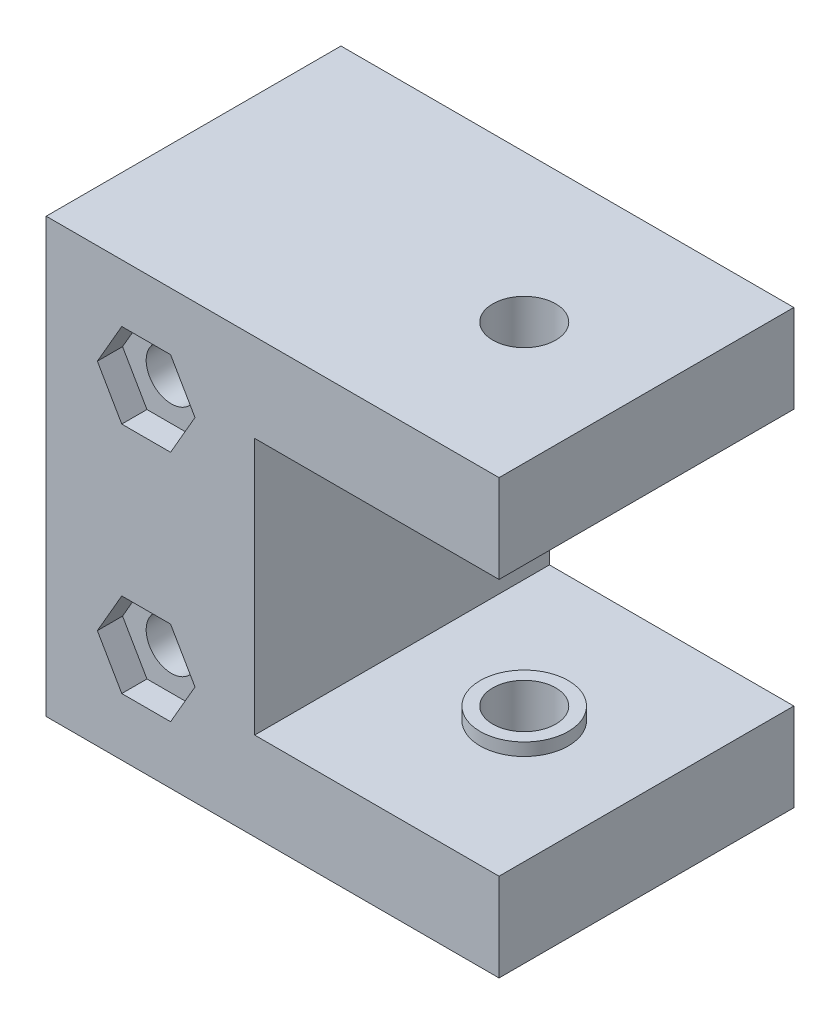
SolidWorks part; units mm, degrees
ref_plane "Front Plane" through (0, 0, 0) normal (0, 0, 1) x (1, 0, 0)
ref_plane "Top Plane" through (0, 0, 0) normal (0, 1, 0) x (1, 0, 0)
ref_plane "Right Plane" through (0, 0, 0) normal (1, 0, 0) x (0, 0, -1)
sketch "MainBlock" plane through (0, 0, 0) normal (0, 0, 1) x (1, 0, 0)
  line L0 (0, 0) -> (35.95, 0)
  line L1 (35.95, 0) -> (35.95, 7)
  line L2 (35.95, 7) -> (16.55, 7)
  line L3 (16.55, 7) -> (16.55, 27.4)
  line L4 (16.55, 27.4) -> (35.95, 27.4)
  line L5 (35.95, 27.4) -> (35.95, 34.4)
  line L6 (35.95, 34.4) -> (0, 34.4)
  line L7 (0, 34.4) -> (0, 0)
  circle A0 centre (7.9375, 26.4625) radius 2
  circle A1 centre (7.9375, 7.9375) radius 2
  dimension "D4" = 4
  dimension "D1" = 35.95
  dimension "D2" = 34.4
  dimension "D3" = 20.4
  dimension "D5" = 19.4
  dimension "D6" = 7.9375
  dimension "D7" = 7.9375
  dimension "D8" = 7.9375
extrude "MainBlockBoss-Extrude1" add sketch "MainBlock" along normal blind 23.4
sketch "TopHoleCut-Sketch2" plane through (0, 34.4, 0) normal (0, 1, 0) x (1, 0, 0)
  line L0 (35.95, 0) -> (0, 0) construction
  line L1 (0, -23.4) -> (0, 0) construction
  circle A0 centre (26.25, -11.7) radius 2.5
  dimension "D3" = 5
  dimension "D1" = 11.7
  dimension "D2" = 26.25
extrude "TopHoleCut-Extrude1" cut sketch "TopHoleCut-Sketch2" against normal blind 30
sketch "MountHoleBoreSketch3" plane through (0, 0, 23.4) normal (0, 0, 1) x (1, 0, 0)
  line L1 (11.8125, 26.4625) -> (9.875, 29.8183)
  line L2 (9.875, 29.8183) -> (6, 29.8183)
  line L3 (6, 29.8183) -> (4.0625, 26.4625)
  line L4 (4.0625, 26.4625) -> (6, 23.1067)
  line L5 (6, 23.1067) -> (9.875, 23.1067)
  line L6 (9.875, 23.1067) -> (11.8125, 26.4625)
  line L7 (11.8125, 7.9375) -> (9.875, 11.2933)
  line L8 (9.875, 11.2933) -> (6, 11.2933)
  line L9 (6, 11.2933) -> (4.0625, 7.9375)
  line L10 (4.0625, 7.9375) -> (6, 4.5817)
  line L11 (6, 4.5817) -> (9.875, 4.5817)
  line L12 (9.875, 4.5817) -> (11.8125, 7.9375)
  circle A0 centre (7.9375, 26.4625) radius 3.3558 construction
  circle A1 centre (7.9375, 7.9375) radius 3.3558 construction
  point P10 (7.9375, 29.8183)
  dimension "D1" = 7.75
extrude "MountHoleBoreCut-Extrude2" cut sketch "MountHoleBoreSketch3" against normal blind 2
sketch "TopSpacerSketch4" plane through (0, 27.4, 0) normal (0, -1, 0) x (1, 0, 0)
  circle A0 centre (26.25, 11.7) radius 3.5
  circle A1 centre (26.25, 11.7) radius 2.5
  circle A2 centre (26.25, 11.7) radius 2.5 construction
  dimension "D1" = 7
extrude "TopSpacerBoss-Extrude2" add sketch "TopSpacerSketch4" along normal blind 1
sketch "LowerSpacerSketch5" plane through (0, 7, 0) normal (0, 1, 0) x (1, 0, 0)
  circle A0 centre (26.25, -11.7) radius 2.5
  circle A1 centre (26.25, -11.7) radius 2.5 construction
  circle A2 centre (26.25, -11.7) radius 3.5
  circle A3 centre (26.25, -11.7) radius 3.5 construction
extrude "LowerSpacerBoss-Extrude3" add sketch "LowerSpacerSketch5" along normal blind 1
sketch "PushPinHoleSketch1" plane through (0, 0, 0) normal (0, -1, 0) x (1, 0, 0)
  circle A0 centre (26.25, 11.7) radius 1
  circle A1 centre (26.25, 11.7) radius 2.5 construction
  dimension "D1" = 2
extrude "PushPinHoleCut-Extrude1" cut sketch "PushPinHoleSketch1" against normal through all
equation "\"BeltTensionerWidth\"= \"MidRailToAlignWithGantryBlock\" + \"BeltTensionerInnerWidth\" / 2"
equation "\"BeltTensionerHeight\"= \"BeltTensionerInnerHeight\" + \"BeltTensionerUpperLowerWallThickness\" * 2"
equation "\"BeltTensionerDepth\"= \"BeltTensionerBackWallThickness\" + \"BeltTensionerInnerDepth\"'Equals 23.4"
equation "\"BeltTensionerUpperLowerWallThickness\"= 7mm"
equation "\"BeltTensionerInnerWidth\"= \"20TGT2PulleyDiameter\" + \"BeltTensionerSpaceBetweenPulleyAndWall\""
equation "\"BeltTensionerInnerHeight\"= \"20TGT2PulleyWidth\" * 2 + \"1mmSpacer\" * 3"
equation "\"BeltTensionerBackWallThickness\"= 4mm"
equation "\"BeltTensionerInnerDepth\"= \"20TGT2PulleyDiameter\" + \"BeltTensionerSpaceBetweenPulleyAndWall\""
equation "\"RailThickness\"= .125in'Spec"
equation "\"HoleOffsetFromEdge\"= \"RailThickness\" * 2.5"
equation "\"LinearGBWithRailDepth\"= 12.75mm'Spec"
equation "\"GABDistanceFromBackToFirstPulley\"= 13.5mm"
equation "\"MidRailToAlignWithGantryBlock\"= \"LinearGBWithRailDepth\" + \"GABDistanceFromBackToFirstPulley\"'All outside cogs must align"
equation "\"20TGT2PulleyDiameter\"= 17.9mm'Spec"
equation "\"BeltTensionerSpaceBetweenPulleyAndWall\"= 1.5mm"
equation "\"BeltTensionerMountingHoleDiameter\"= 4.0mm"
equation "\"BeltTensionerMountingHoleOffsetFromEdge\"= \"HoleOffsetFromEdge\""
equation "\"20TGT2PulleyWidth\"= 8.7mm'The STL of the Pulley in the diagram is a bit larger"
equation "\"1mmSpacer\"= 1mm"
equation "\"SteelShaft5mmHoleDiameter\"= 5mm"
equation "\"BeltTensionerMountingHoleOuterBoreDepth\"= 2mm"
equation "\"BeltTensionerMountingHoleOuterBoreDiameter\"= 7.75mm'From the100"
equation "\"7mmx1mmSpacerDiameter\"= 7mm"
equation "\"7mmx1mmSpacerHeight\"= 1mm"
equation "\"D1@MainBlock\" = \"BeltTensionerWidth\""
equation "\"D2@MainBlock\" = \"BeltTensionerHeight\""
equation "\"D3@MainBlock\" = \"BeltTensionerInnerHeight\""
equation "\"D4@MainBlock\" = \"BeltTensionerMountingHoleDiameter\""
equation "\"D5@MainBlock\" = \"BeltTensionerInnerWidth\""
equation "\"D6@MainBlock\"=\"BeltTensionerMountingHoleOffsetFromEdge\""
equation "\"D7@MainBlock\" = \"HoleOffsetFromEdge\""
equation "\"D8@MainBlock\" = \"HoleOffsetFromEdge\""
equation "\"D1@MainBlockBoss-Extrude1\" = \"BeltTensionerDepth\""
equation "\"D1@TopHoleCut-Sketch2\" = \"BeltTensionerDepth\" / 2"
equation "\"D2@TopHoleCut-Sketch2\" = \"MidRailToAlignWithGantryBlock\""
equation "\"D3@TopHoleCut-Sketch2\" = \"SteelShaft5mmHoleDiameter\""
equation "\"D1@MountHoleBoreSketch3\" = \"BeltTensionerMountingHoleOuterBoreDiameter\""
equation "\"D1@MountHoleBoreCut-Extrude2\"=\"BeltTensionerMountingHoleOuterBoreDepth\""
equation "\"D1@TopSpacerSketch4\" = \"7mmx1mmSpacerDiameter\""
equation "\"D1@TopSpacerBoss-Extrude2\" = \"7mmx1mmSpacerHeight\""
equation "\"D1@LowerSpacerBoss-Extrude3\" = \"7mmx1mmSpacerHeight\""
equation "\"StealPinPushHoleDiameter\"= 2mm"
equation "\"D1@PushPinHoleSketch1\" = \"StealPinPushHoleDiameter\""
